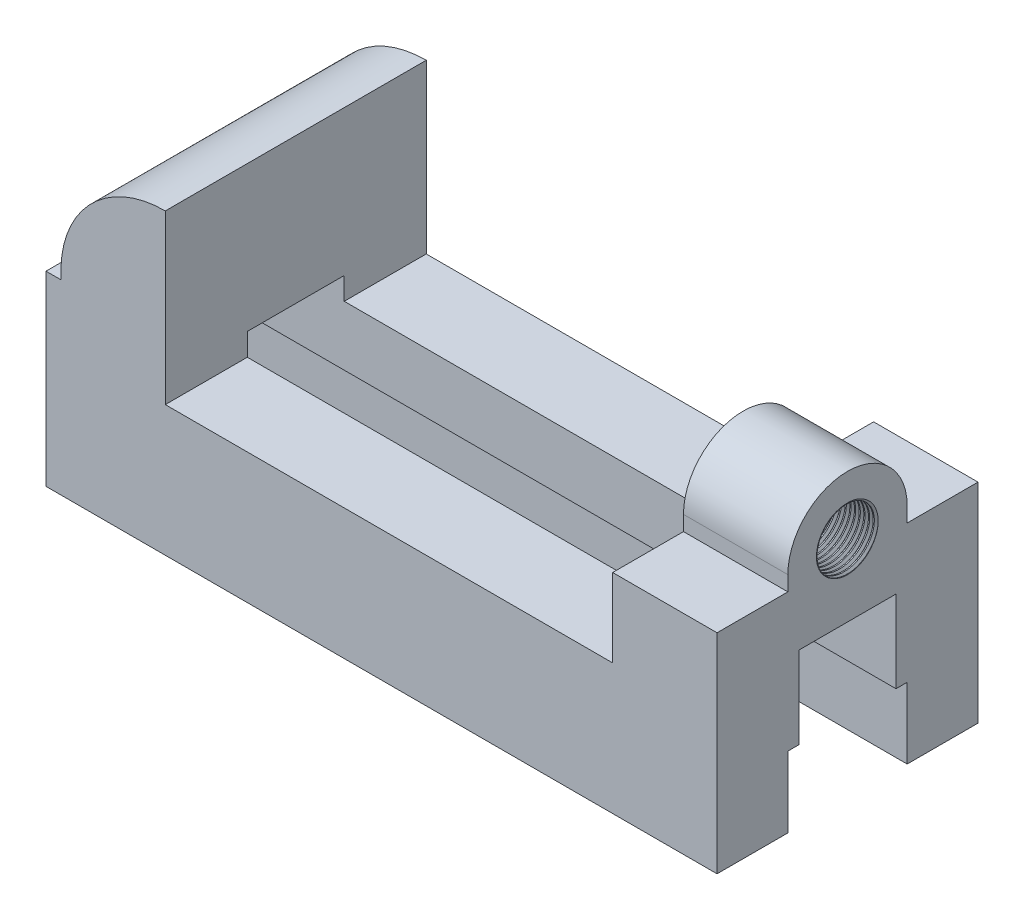
SolidWorks part; units mm, degrees
note: The reader was unsure of these and kept them because the rebuilt part matched: shared geometry of "Sketch3<2>".
ref_plane "Front Plane" through (0, 0, 0) normal (0, 0, 1) x (1, 0, 0)
ref_plane "Top Plane" through (0, 0, 0) normal (0, 1, 0) x (1, 0, 0)
ref_plane "Right Plane" through (0, 0, 0) normal (1, 0, 0) x (0, 0, -1)
sketch "Sketch1" plane through (0, 0, 0) normal (0, 0, 1) x (1, 0, 0)
  line L1 (0, 0) -> (180, 0)
  line L2 (0, 0) -> (0, 80)
  line L3 (0, 80) -> (180, 80)
  line L4 (180, 0) -> (180, 80)
  dimension "D1" = 180
  dimension "D2" = 80
extrude "Boss-Extrude1" add sketch "Sketch1" against normal blind 70
sketch "Sketch2" plane through (0, 0, 0) normal (0, 0, 1) x (1, 0, 0)
  line L0 (0, 50) -> (4.0715, 50)
  line L1 (0, 80) -> (0, 0) construction
  line L2 (180, 80) -> (0, 80) construction
  line L3 (0, 0) -> (180, 0) construction
  line L4 (32, 80) -> (32, 35)
  line L5 (180, 56) -> (152, 56)
  line L6 (32, 80) -> (180, 80)
  line L7 (180, 0) -> (180, 80) construction
  line L8 (152, 56) -> (152, 35)
  line L9 (152, 35) -> (32, 35)
  line L10 (180, 80) -> (180, 56)
  line L11 (0, 50) -> (0, 80)
  line L12 (0, 80) -> (32, 80)
  arc A0 (4.0715, 50) -> (32, 80) centre (32, 52) cw
  line M5 (0, 80) -> (0, 0)
  line M7 (180, 0) -> (180, 80)
  line M8 (180, 80) -> (0, 80)
  dimension "D3" = 28
  dimension "D1" = 32
  dimension "D2" = 50
  dimension "D4" = 56
  dimension "D5" = 28
  dimension "D6" = 35
extrude "Cut-Extrude1" cut sketch "Sketch2" against normal up to next contours L9 L8 L5 L4 M7 M8 | L0 A0 M8 M5
sketch "Sketch3" plane through (180, 0, 0) normal (1, 0, 0) x (0, 0, -1)
  line L1 (70, 0) -> (0, 0) construction
  line L2 (70, 35) -> (0, 35) construction
  line L3 (19, 60) -> (19, 56)
  line L4 (70, 56) -> (0, 56) construction
  line L5 (51, 60) -> (51, 56)
  line L6 (51, 56) -> (41.9282, 56)
  line L7 (28.0718, 56) -> (19, 56)
  arc A0 (51, 60) -> (19, 60) centre (35, 60) ccw
  arc A1 (41.9282, 56) -> (28.0718, 56) centre (35, 60) ccw
  arc A2 (28.0718, 56) -> (41.9282, 56) centre (35, 60) ccw
  point P7 (35, 0)
  line M2 (70, 56) -> (0, 56)
  dimension "D1" = 32
  dimension "D2" = 16
  dimension "D3" = 25
extrude "Boss-Extrude2" add sketch "Sketch3" against normal up to surface (28 mm away) contours A1 L5 A0 L3 M2 up to face at (152, 45.5, -35)
extrude "Cut-Extrude2" cut sketch "Sketch3<2>" against normal up to surface (28 mm away) contours A1 M2 | A2 M2 up to face at (152, 53.75, -35)
sketch "Sketch3<2>" plane through (180, 0, 0) normal (1, 0, 0) x (0, 0, -1) same geometry as "Sketch3"
sketch "Sketch4" plane through (0, 35, 0) normal (0, 1, 0) x (1, 0, 0)
  line L0 (152, 51) -> (152, 19) construction
  line L1 (152, 48) -> (32, 48)
  line L2 (152, 48) -> (152, 22)
  line L3 (152, 22) -> (32, 22)
  line L4 (32, 48) -> (32, 22)
  line L5 (32, 70) -> (32, 0) construction
  line L6 (152, 70) -> (32, 70) construction
  line L7 (152, 0) -> (32, 0) construction
  dimension "D1" = 22
  dimension "D2" = 22
extrude "Boss-Extrude3" add sketch "Sketch4" along normal blind 6
sketch "Sketch5" plane through (0, 0, 0) normal (-1, 0, 0) x (0, 0, 1)
  line L0 (-51, 0) -> (-51, 19)
  line L1 (-70, 0) -> (0, 0) construction
  line L2 (-51, 19) -> (-48, 19)
  line L3 (-48, 19) -> (-48, 41)
  line L4 (-48, 41) -> (-22, 41)
  line L5 (-22, 41) -> (-22, 19)
  line L6 (-22, 19) -> (-19, 19)
  line L7 (-19, 19) -> (-19, 0)
  line L8 (-19, 0) -> (-51, 0)
  line L9 (-70, 50) -> (-70, 0) construction
  line L10 (0, 50) -> (0, 0) construction
  line L11 (-35, 0) -> (-35, 20.8831) construction
  dimension "D1" = 19
  dimension "D2" = 19
  dimension "D3" = 19
  dimension "D4" = 22
  dimension "D5" = 22
extrude "Cut-Extrude3" cut sketch "Sketch5" against normal through all
thread "Thread1" pitch 1.25 profile "Thread Profile1" start angle 0, offset 2, length 40, pitch 1.25, diameter 16
ref_plane "Plane1" through (182, 60, -27) normal (0, -1, 0) x (0, 0, 1)
sketch "Thread Profile1" plane through (182, 60, -27) normal (0, -1, 0) x (0, 0, 1)
  line L0 (0, 0) -> (0, 1.25) construction
  line L1 (0, 0) -> (0.6766, 0.3906)
  line L2 (0.6766, 0.3906) -> (0.6766, 0.5469)
  line L3 (0.6766, 0.5469) -> (0, 0.9375)
  line L4 (0.6766, 0.4687) -> (0, 0.4687) construction
  line L11 (0, 0) -> (0, 0.9375)
  point P2 (0, 0)
  dimension "Pitch" = 1.25
  dimension "Profile_Angle" = 60
  dimension "Profile_Land" = 0.1562
  dimension "Profile_Height" = 0.6766
